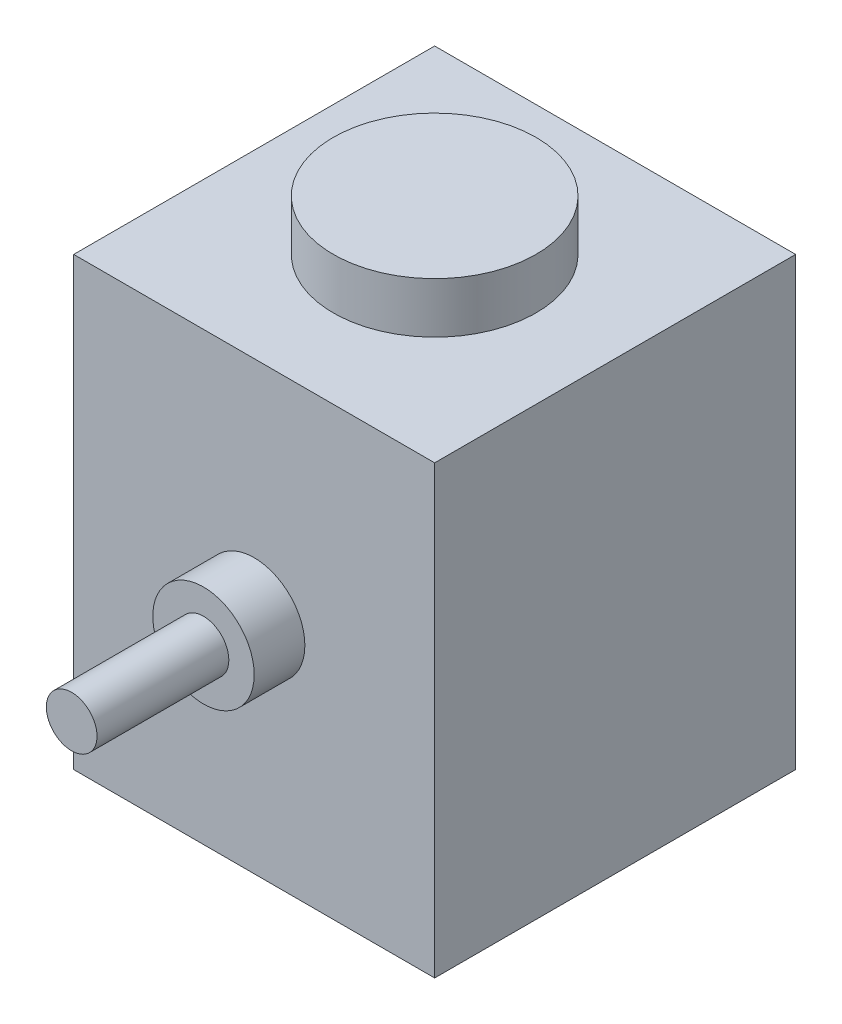
SolidWorks part; units mm, degrees
ref_plane "Front Plane" through (0, 0, 0) normal (1, 0, 0) x (0, 1, 0)
ref_plane "Top Plane" through (0, 0, 0) normal (0, 0, 1) x (0, 1, 0)
ref_plane "Right Plane" through (0, 0, 0) normal (0, 1, 0) x (-1, 0, 0)
sketch "Sketch1" plane through (0, 0, 0) normal (1, 0, 0) x (0, 1, 0)
  line L0 (0, 0) -> (68.58, 0)
  line L1 (68.58, 0) -> (68.58, 45.212)
  line L2 (68.58, 45.212) -> (0, 45.212)
  line L3 (0, 45.212) -> (0, 0)
  line L4 (68.58, 35.306) -> (68.58, 9.906)
  line L5 (68.58, 9.906) -> (62.23, 9.906)
  line L6 (62.23, 9.906) -> (62.23, 35.306)
  line L7 (62.23, 35.306) -> (68.58, 35.306)
  line L8 (0, 35.306) -> (0, 9.906)
  line L9 (0, 9.906) -> (6.35, 9.906)
  line L10 (6.35, 9.906) -> (6.35, 35.306)
  line L11 (6.35, 35.306) -> (0, 35.306)
  line L12 (6.35, 22.606) -> (62.23, 22.606)
  line L13 (6.35, 35.306) -> (6.35, 45.212)
  line L14 (6.35, 9.906) -> (6.35, 0)
  line L15 (62.23, 35.306) -> (62.23, 45.212)
  line L16 (62.23, 9.906) -> (62.23, 0)
  line L17 (6.35, 45.212) -> (6.35, 70.612)
  line L18 (6.35, 70.612) -> (0, 70.612)
  line L19 (0, 70.612) -> (0, 45.212)
  line L20 (62.23, 45.212) -> (62.23, 70.612)
  line L21 (62.23, 70.612) -> (68.58, 70.612)
  line L22 (68.58, 70.612) -> (68.58, 45.212)
  dimension "D1" = 68.58
  dimension "D2" = 45.212
  dimension "D3" = 6.35
  dimension "D4" = 6.35
  dimension "D5" = 25.4
  dimension "D6" = 25.4
  dimension "D7" = 9.906
  dimension "D8" = 9.906
  dimension "D9" = 12.7
  dimension "D10" = 25.4
  dimension "D11" = 25.4
extrude "Boss-Extrude1" add sketch "Sketch1" along normal blind 22.606 and the other way blind 22.606 contours L6 L15 L2 L13 L10 L12 | L10 L11 L3 L9 | L16 L6 L12 L10 L14 L0 | L7 L6 L5 L1 region at (0, 34.29, 11.303) region at (0, 3.175, 22.606) region at (0, 65.405, 22.606) region at (0, 34.29, 33.909)
revolve "Cut-Revolve3" cut sketch "Sketch1<5>" angle 360 about L12 region at (0, 3.175, 40.259) region at (0, 3.175, 57.912) region at (0, 65.405, 40.259) region at (0, 65.405, 57.912)
sketch "Sketch1<5>" plane through (0, 0, 0) normal (1, 0, 0) x (0, 1, 0) same geometry as "Sketch1"
sketch "Sketch2" plane through (0, 0, 45.212) normal (0, 0, 1) x (1, 0, 0)
  line L0 (0, 6.35) -> (0, 34.29)
  line L1 (-22.606, 6.35) -> (22.606, 6.35) construction
  line L2 (0, 34.29) -> (22.606, 34.29)
  line L3 (22.606, 62.23) -> (22.606, 6.35) construction
  circle A0 centre (0, 34.29) radius 3.175
  circle A1 centre (0, 34.29) radius 6.35
  dimension "D1" = 6.35
  dimension "D2" = 12.7
extrude "Boss-Extrude2" add sketch "Sketch2" along normal blind 22.86 contours L2 A0 L0 | L0 A0 L2 region at (-0.4492, 34.7392, 45.212) region at (1.3475, 32.9425, 45.212)
extrude "Boss-Extrude3" add sketch "Sketch2<3>" along normal blind 6.35 contours L0 A1 L2 A0 | L2 A1 L0 A0 region at (-4.3631, 38.6531, 45.212) region at (3.1442, 31.1458, 45.212)
sketch "Sketch2<3>" plane through (0, 0, 45.212) normal (0, 0, 1) x (1, 0, 0) same geometry as "Sketch2"
